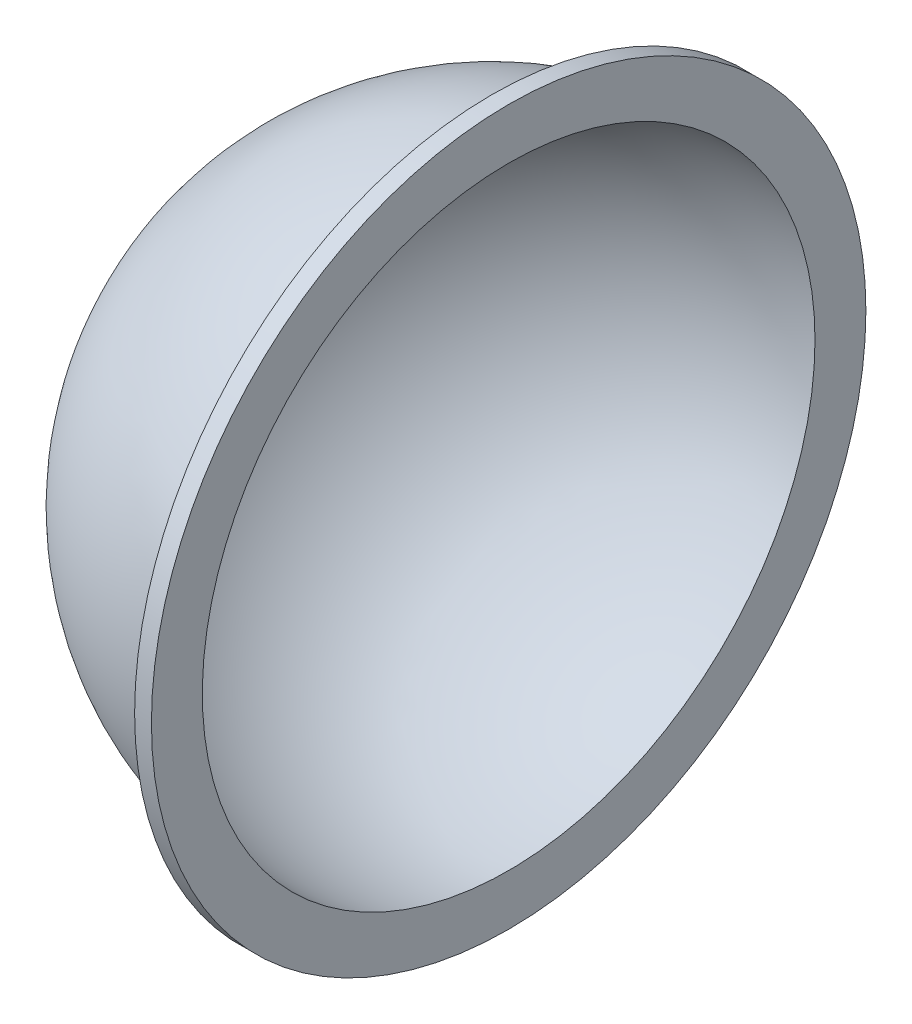
SolidWorks part; units mm, degrees
ref_plane "Front Plane" through (0, 0, 0) normal (0, 0, 1) x (1, 0, 0)
ref_plane "Top Plane" through (0, 0, 0) normal (0, 1, 0) x (1, 0, 0)
ref_plane "Right Plane" through (0, 0, 0) normal (1, 0, 0) x (0, 0, -1)
sketch "Sketch1" plane through (0, 0, 0) normal (0, 0, 1) x (1, 0, 0)
  line L0 (0, 36.5) -> (0, 57.3704)
  line L1 (0, 0) -> (-57.2513, 0)
  line L2 (0, 0) -> (2, 0)
  line L3 (2, 36.4452) -> (2, 57.3704)
  line L4 (2, -2) -> (-57.2513, -2) construction
  line L5 (2, -2) -> (2, 57.3704) construction
  line L6 (0, 42.5) -> (2, 42.5)
  line L7 (0, 0) -> (0, 57.3704) construction
  arc A0 (2, 37.4466) -> (-37.5, 0) centre (0, 0) ccw
  arc A1 (2, 36.4452) -> (-36.5, 0) centre (0, 0) ccw
  dimension "D1" = 2
  dimension "D2" = 42.5
  dimension "D3" = 75
  dimension "D4" = 73
revolve "Revolve1" add sketch "Sketch1" angle 360 about L1 region at (-26.1844, 26.1844, 0) region at (1.0002, 36.982, 0) region at (1.0018, 39.9911, 0)
